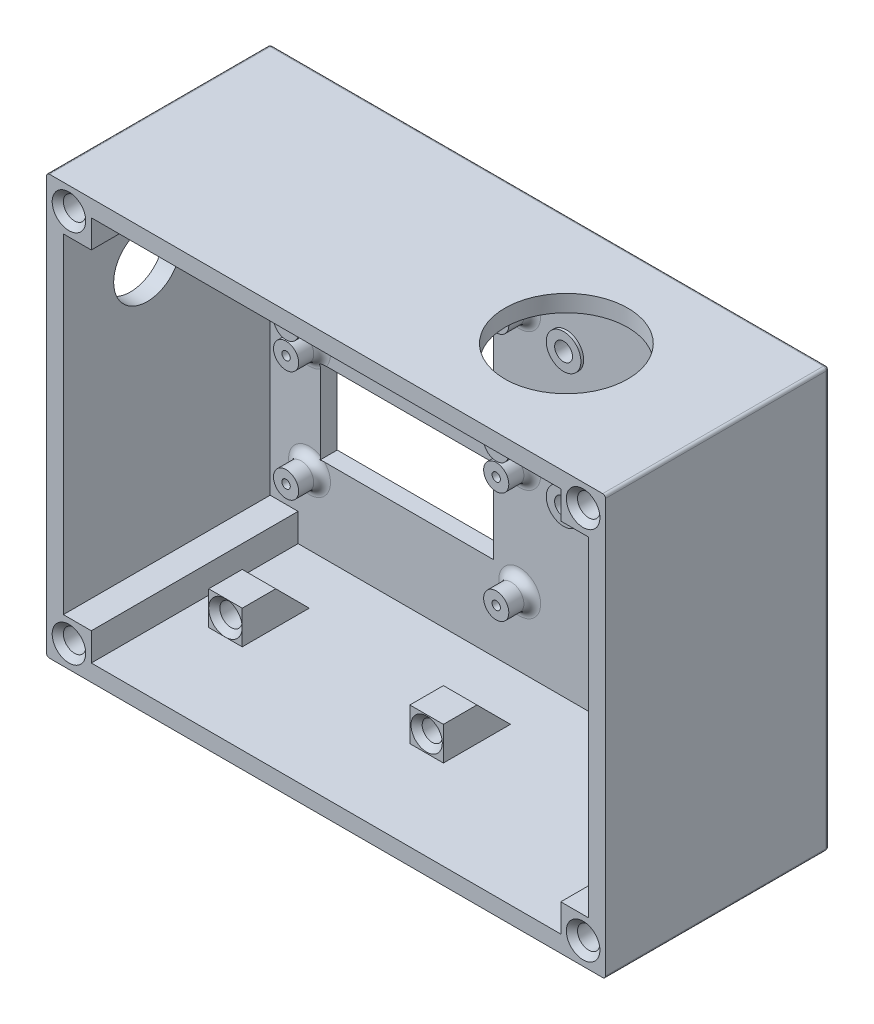
SolidWorks part; units mm, degrees
ref_plane "Płaszczyzna przednia" through (0, 0, 0) normal (0, 0, 1) x (1, 0, 0)
ref_plane "Płaszczyzna górna" through (0, 0, 0) normal (0, 1, 0) x (1, 0, 0)
ref_plane "Płaszczyzna prawa" through (0, 0, 0) normal (1, 0, 0) x (0, 0, -1)
sketch "Szkic1" plane through (0, 0, 0) normal (0, 0, 1) x (1, 0, 0)
  line L1 (-50, 37.5) -> (50, 37.5)
  line L2 (-50, 37.5) -> (-50, -37.5)
  line L3 (-50, -37.5) -> (50, -37.5)
  line L4 (50, 37.5) -> (50, -37.5)
  line L5 (-50, 37.5) -> (50, -37.5) construction
  line L6 (-50, -37.5) -> (50, 37.5) construction
  point P0 (0, 0)
  dimension "D1" = 100
  dimension "D2" = 75
extrude "Dodanie-wyciągnięcie1" add sketch "Szkic1" along normal blind 40
shell "Skorupa1" thickness 3 removed face at (0, 0, 40)
sketch "Szkic2" plane through (0, 0, 0) normal (0, 0, -1) x (-1, 0, 0)
  line L0 (7.5, -19) -> (37.5, -19) construction
  line L1 (37.5, -19) -> (37.5, -5) construction
  line L2 (37.5, -5) -> (7.5, -5) construction
  line L3 (7.5, -5) -> (7.5, -19) construction
  line L4 (7.5, 5.6) -> (37.5, 5.6) construction
  line L5 (37.5, 5.6) -> (37.5, 19.6) construction
  line L6 (37.5, 19.6) -> (7.5, 19.6) construction
  line L7 (7.5, 19.6) -> (7.5, 5.6) construction
  line L8 (7.5, -19) -> (37.5, -19) construction
  line L9 (37.5, -19) -> (37.5, -5) construction
  line L10 (37.5, -5) -> (7.5, -5) construction
  line L11 (7.5, -5) -> (7.5, -19) construction
  line L12 (7.5, 5.6) -> (37.5, 5.6) construction
  line L13 (37.5, 5.6) -> (37.5, 19.6) construction
  line L14 (37.5, 19.6) -> (7.5, 19.6) construction
  line L15 (7.5, 19.6) -> (7.5, 5.6) construction
  line L16 (7, -19.5) -> (38, -19.5)
  line L17 (38, -19.5) -> (38, -4.5)
  line L18 (38, -4.5) -> (7, -4.5)
  line L19 (7, -4.5) -> (7, -19.5)
  line L20 (7, 5.1) -> (38, 5.1)
  line L21 (38, 5.1) -> (38, 20.1)
  line L22 (38, 20.1) -> (7, 20.1)
  line L23 (7, 20.1) -> (7, 5.1)
  dimension "D1" = 0.5
extrude "Wytnij-wyciągnięcie1" cut sketch "Szkic2" against normal up to next
sketch "Szkic3" plane through (0, 0, 0) normal (0, 0, -1) x (-1, 0, 0)
  circle A0 centre (-6, -4.4764) radius 1.4991 construction
  circle A1 centre (-6, 7.5236) radius 1.4991 construction
  circle A2 centre (-6, 19.5236) radius 1.4991 construction
  circle A3 centre (-6, -4.4764) radius 1.4991 construction
  circle A4 centre (-6, 7.5236) radius 1.4991 construction
  circle A5 centre (-6, 19.5236) radius 1.4991 construction
  circle A6 centre (-6, -4.4764) radius 1.5991
  circle A7 centre (-6, 7.5236) radius 1.5991
  circle A8 centre (-6, 19.5236) radius 1.5991
  dimension "D1" = 0.1
extrude "Wytnij-wyciągnięcie2" cut sketch "Szkic3" against normal up to next
sketch "Szkic4" plane through (0, 37.5, 0) normal (0, 1, 0) x (1, 0, 0)
  line L0 (50, -40) -> (50, 0) construction
  circle A0 centre (23, -20) radius 11
  point P4 (50, -20)
  dimension "D1" = 22
  dimension "D2" = 27
extrude "Wytnij-wyciągnięcie3" cut sketch "Szkic4" against normal up to next
sketch "Szkic6" plane through (0, 0, 0) normal (0, 0, -1) x (-1, 0, 0)
  line L0 (-33.25, -33) -> (-14.15, -33)
  line L1 (-14.15, -33) -> (-14.15, -20.5)
  line L2 (-14.15, -20.5) -> (-33.25, -20.5)
  line L3 (-33.25, -20.5) -> (-33.25, -33)
  line L4 (-32.75, -32.5) -> (-14.65, -32.5)
  line L5 (-32.75, -21) -> (-32.75, -32.5)
  line L6 (-14.65, -21) -> (-32.75, -21)
  line L7 (-14.65, -32.5) -> (-14.65, -21)
  line L8 (-32.75, -32.5) -> (-14.65, -32.5) construction
  line L9 (-32.75, -21) -> (-32.75, -32.5) construction
  line L10 (-14.65, -21) -> (-32.75, -21) construction
  line L11 (-14.65, -32.5) -> (-14.65, -21) construction
  dimension "D1" = 0
  dimension "D2" = 0.5
extrude "Wytnij-wyciągnięcie4" cut sketch "Szkic6" against normal up to next
sketch "Szkic7" plane through (0, 0, 3) normal (0, 0, 1) x (1, 0, 0)
  line L1 (47, -34.5) -> (42, -34.5)
  line L2 (47, -34.5) -> (47, -29.5)
  line L3 (47, -29.5) -> (42, -29.5)
  line L4 (42, -34.5) -> (42, -29.5)
  line L5 (47, 34.5) -> (42, 34.5)
  line L6 (47, 34.5) -> (47, 29.5)
  line L7 (47, 29.5) -> (42, 29.5)
  line L8 (42, 34.5) -> (42, 29.5)
  line L9 (-47, 34.5) -> (-42, 34.5)
  line L10 (-47, 34.5) -> (-47, 29.5)
  line L11 (-47, 29.5) -> (-42, 29.5)
  line L12 (-42, 34.5) -> (-42, 29.5)
  line L13 (-47, -34.5) -> (-42, -34.5)
  line L14 (-47, -34.5) -> (-47, -29.5)
  line L15 (-47, -29.5) -> (-42, -29.5)
  line L16 (-42, -34.5) -> (-42, -29.5)
  dimension "D1" = 5
extrude "Dodanie-wyciągnięcie2" add sketch "Szkic7" along normal up to surface (37 mm away) up to face at (0, 0, 40)
hole_wizard "Otwory ustalające Ø4.0mm1" positions "Szkic8" profile "Szkic9" hole size "Ø4.0" standard "Ansi Metric"
sketch "Szkic8" plane through (0, 0, 40) normal (0, 0, 1) x (1, 0, 0)
  line L0 (50, 37.5) -> (-50, 37.5) construction
  line L1 (-50, 37.5) -> (-50, -37.5) construction
  point P0 (-46, 33.5)
  point P2 (46, 33.5)
  point P4 (46, -33.5)
  point P6 (-46, -33.5)
  point P9 (0, 0)
  point P10 (0, 0)
  point P11 (0, 0)
  point P12 (0, 0)
  point P13 (0, 0)
  point P16 (0, 37.5)
  point P19 (-50, 0)
  dimension "D1" = 46
  dimension "D2" = 33.5
  dimension "D3" = 92
  dimension "D4" = 67
sketch "Szkic9" plane through (-46, 33.5, 40) normal (1, 0, 0) x (0, -1, 0)
  line L0 (0, 0) -> (0, 16.2017)
  line L1 (0, 16.2017) -> (2, 15)
  line L2 (2, 15) -> (2, 0)
  line L5 (2, 0) -> (0, 0)
  line L10 (0, 16.2017) -> (-2, 15) construction
  line L11 (0, -6.35) -> (0, 107.95) construction
  dimension "Średnica otworu" = 4
  dimension "Głębokość otworu" = 15
  dimension "Kąt wiertła" = 118
sketch "Szkic10" plane through (-50, 0, 0) normal (-1, 0, 0) x (0, 0, 1)
  line L2 (40, -37.5) -> (0, -37.5) construction
  line L4 (40, 37.5) -> (40, -37.5) construction
  circle A1 centre (25, 17.5) radius 6
  point P6 (40, -10.7113)
  dimension "D1" = 12
  dimension "D3" = 15
  dimension "D2" = 55
extrude "Wytnij-wyciągnięcie5" cut sketch "Szkic10" against normal up to next
sketch "Szkic11" plane through (0, 0, 3) normal (0, 0, 1) x (1, 0, 0)
  line L0 (-42, -34.5) -> (42, -34.5) construction
  line L1 (-37, -34.5) -> (-31, -34.5)
  line L2 (-37, -34.5) -> (-37, -28.5)
  line L3 (-37, -28.5) -> (-31, -28.5)
  line L4 (-31, -34.5) -> (-31, -28.5)
  line L5 (-42, -34.5) -> (-42, -29.5) construction
  line L6 (-1, -34.5) -> (5, -34.5)
  line L7 (-1, -34.5) -> (-1, -28.5)
  line L8 (-1, -28.5) -> (5, -28.5)
  line L9 (5, -34.5) -> (5, -28.5)
  circle A0 centre (-34, -31.5) radius 2
  circle A1 centre (2, -31.5) radius 1.7982
  point P16 (0, 0)
  point P17 (-34, -28.5)
  point P18 (0, 0)
  point P19 (2, -28.5)
  point P20 (0, 0)
  point P21 (-37, -31.5)
  dimension "D4" = 4
  dimension "D1" = 6
  dimension "D2" = 5
  dimension "D3" = 30
extrude "Dodanie-wyciągnięcie3" add sketch "Szkic11" along normal blind 6 from offset 15
chamfer "Sfazowanie1" distance 6 angle 45 1 edges at (2, -34.5, 18)
chamfer "Sfazowanie2" distance 6 angle 45 1 edges at (-34, -34.5, 18)
sketch "Szkic12" plane through (0, 0, 0) normal (0, 0, -1) x (-1, 0, 0)
  text T0 "<b>BAT. LOGIKI</b>"
  text T1 "<b>BAT. SILNIKÓW</b>"
  text T2 "<b>ZASILANIE</b>"
  text T3 "<b>POŁĄCZENIE</b>"
  text T4 "<b>ON</b>"
  text T5 "<b>OFF</b>"
  text T6 "<b>AWARIA</b>"
  point P1 (0, 0)
  point P3 (-1.933, -1.2261)
  point P4 (0, 0)
  point P5 (0, -2.0071)
  point P6 (0, 0)
  point P7 (0, 0)
  point P8 (8.3175, 21.9107)
  point P9 (0, 0)
  point P10 (0, 0)
  point P11 (9.5866, 21.6178)
  point P12 (0, 0)
  point P13 (0, 0)
  point P14 (9.0985, 21.7154)
  point P16 (-30.7119, 18.8416)
  point P17 (0, 0)
  point P18 (0, 0)
  point P19 (-30.8088, 17.7763)
  point P20 (-30.6151, 18.0668)
  point P21 (-30.3246, 17.2921)
  point P22 (-29.6466, 17.3889)
  point P23 (-29.3561, 17.5826)
  point P24 (-29.7435, 17.8731)
  point P26 (-36.8131, 4.896)
  point P27 (-38.75, 5.6708)
  point P28 (-40.2995, 5.7676)
  point P31 (-38.4612, -16.411)
  point P32 (0, 0)
  point P33 (-38.577, -16.411)
  point P34 (-44.1329, -28.3331)
  point P35 (-45.4061, -28.3331)
  point P36 (-11.0289, -28.3331)
  point P37 (-46.6794, -28.3331)
  point P38 (-33.4672, 17.8423)
  point P40 (-27.2013, -6.2592)
  point P41 (-32.1151, -6.7272)
  point P42 (-31.5302, -6.1422)
  point P43 (-30.3602, -6.2592)
  point P44 (-30.3602, -6.7272)
  point P45 (-30.7112, -6.8442)
  point P46 (-30.7112, -6.6102)
  point P47 (-30.7112, -6.1422)
  point P48 (-30.9452, -6.7272)
  point P49 (-30.5942, -6.3762)
  point P50 (-40.0136, 5.8271)
  point P51 (-39.7882, 5.6764)
  point P52 (-39.3005, 5.69)
  point P53 (-39.1777, 5.6286)
  point P54 (-39.4847, 5.5672)
  point P55 (-30.2744, -6.2834)
extrude "Wytnij-wyciągnięcie6" cut sketch "Szkic12" against normal blind 1
fillet "Zaokrąglenie1" radius 0.5 8 edges at (0, 37.5, 0) (-50, 0, 0) (0, -37.5, 0) (50, -37.5, 20) (-50, -37.5, 20) (-50, 37.5, 20) (50, 37.5, 20) (50, 0, 0)
chamfer "Sfazowanie3" distance 1 angle 45 6 edges at (3.7982, -31.5, 24) (-32, -31.5, 24) (-44, -33.5, 40) (48, -33.5, 40) (48, 33.5, 40) (-44, 33.5, 40)
sketch "Szkic13" plane through (0, 0, 3) normal (0, 0, 1) x (1, 0, 0)
  circle A0 centre (-2.35, -22.15) radius 1.25 construction
  circle A1 centre (-39.95, -22.15) radius 1.25 construction
  circle A2 centre (-2.35, -2.25) radius 1.25 construction
  circle A3 centre (-39.95, -2.25) radius 1.25 construction
  circle A4 centre (-2.35, 2.45) radius 1.25 construction
  circle A5 centre (-39.95, 2.45) radius 1.25 construction
  circle A6 centre (-39.95, 22.35) radius 1.25 construction
  circle A7 centre (-2.35, 22.35) radius 1.25 construction
  circle A8 centre (-2.35, -22.15) radius 1.25 construction
  circle A9 centre (-39.95, -22.15) radius 1.25 construction
  circle A10 centre (-2.35, -2.25) radius 1.25 construction
  circle A11 centre (-39.95, -2.25) radius 1.25 construction
  circle A12 centre (-2.35, 2.45) radius 1.25 construction
  circle A13 centre (-39.95, 2.45) radius 1.25 construction
  circle A14 centre (-39.95, 22.35) radius 1.25 construction
  circle A15 centre (-2.35, 22.35) radius 1.25 construction
  circle A16 centre (-2.35, -22.15) radius 0.75
  circle A17 centre (-39.95, -22.15) radius 0.75
  circle A18 centre (-2.35, -2.25) radius 0.75
  circle A19 centre (-39.95, -2.25) radius 0.75
  circle A20 centre (-2.35, 2.45) radius 0.75
  circle A21 centre (-39.95, 2.45) radius 0.75
  circle A22 centre (-39.95, 22.35) radius 0.75
  circle A23 centre (-2.35, 22.35) radius 0.75
  circle A24 centre (-2.35, -22.15) radius 2.25
  circle A25 centre (-39.95, -22.15) radius 2.25
  circle A26 centre (-39.95, -2.25) radius 2.25
  circle A27 centre (-39.95, 2.45) radius 2.25
  circle A28 centre (-2.35, -2.25) radius 2.25
  circle A29 centre (-2.35, 2.45) radius 2.25
  circle A30 centre (-2.35, 22.35) radius 2.25
  circle A31 centre (-39.95, 22.35) radius 2.25
  dimension "D1" = 1.5
  dimension "D2" = 1.5
extrude "Dodanie-wyciągnięcie4" add sketch "Szkic13" along normal blind 4.2
fillet "Zaokrąglenie2" radius 1.5 8 edges at (-0.1, 22.35, 3) (-37.7, 22.35, 3) (-37.7, 2.45, 3) (-37.7, -2.25, 3) (-37.7, -22.15, 3) (-0.1, -22.15, 3) (-0.1, -2.25, 3) (-0.1, 2.45, 3)
sketch "Szkic14" plane through (0, 0, 3) normal (0, 0, 1) x (1, 0, 0)
  circle A0 centre (6, -4.4764) radius 1.5991 construction
  circle A1 centre (6, 7.5236) radius 1.5991 construction
  circle A2 centre (6, 19.5236) radius 1.5991 construction
  circle A3 centre (6, -4.4764) radius 1.5991
  circle A4 centre (6, 7.5236) radius 1.5991
  circle A5 centre (6, 19.5236) radius 1.5991
  circle A6 centre (6, -4.4764) radius 3.0991
  circle A7 centre (6, 7.5236) radius 3.0991
  circle A8 centre (6, 19.5236) radius 3.0991
  dimension "D1" = 1.5
extrude "Dodanie-wyciągnięcie5" add sketch "Szkic14" along normal blind 0.5
equation "\"D1@Szkic8\"=\"D3@Szkic8\"/2"
equation "\"D2@Szkic8\"=\"D4@Szkic8\"/2"
